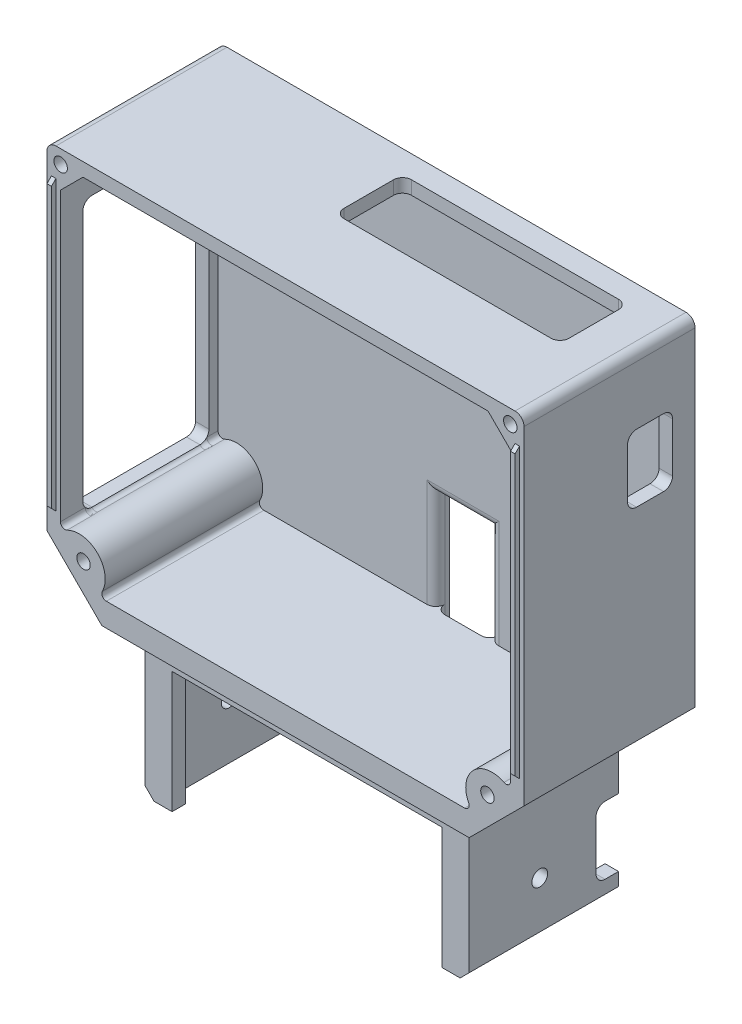
SolidWorks part; units mm, degrees
ref_plane "Front Plane" through (0, 0, 0) normal (0, 0, 1) x (1, 0, 0)
ref_plane "Top Plane" through (0, 0, 0) normal (0, 1, 0) x (1, 0, 0)
ref_plane "Right Plane" through (0, 0, 0) normal (1, 0, 0) x (0, 0, -1)
sketch "Sketch1" plane through (0, 0, 0) normal (0, 0, 1) x (1, 0, 0)
  line L1 (53, -42.5) -> (-53, -42.5)
  line L2 (53, -42.5) -> (53, 42.5)
  line L3 (53, 42.5) -> (-53, 42.5)
  line L4 (-53, -42.5) -> (-53, 42.5)
  line L5 (53, -42.5) -> (-53, 42.5) construction
  line L6 (53, 42.5) -> (-53, -42.5) construction
  point P0 (0, 0)
  dimension "D1" = 85
  dimension "D2" = 106
extrude "Boss-Extrude1" add sketch "Sketch1" along normal blind 38
chamfer "Chamfer1" distance 10 angle 45 2 edges at (-53, -42.5, 19) (53, -42.5, 19)
shell "Shell1" thickness 3 removed face at (0, -10.8333, 38)
sketch "Sketch2" plane through (0, -42.5, 0) normal (0, -1, 0) x (1, 0, 0)
  line L0 (-43, 0) -> (43, 0) construction
  line L1 (36, 0) -> (33, 0)
  line L2 (36, 0) -> (36, 33.2)
  line L7 (0, 0) -> (0, 38) construction
  line L8 (-43, 38) -> (43, 38) construction
  line L11 (-36, 0) -> (-36, 33.2)
  line L12 (-36, 0) -> (-33, 0)
  line L13 (-36, 33.2) -> (36, 33.2)
  line L14 (33, 0) -> (33, 30.2)
  line L15 (33, 30.2) -> (-33, 30.2)
  line L16 (-33, 30.2) -> (-33, 0)
  dimension "D1" = 33
  dimension "D2" = 3
  dimension "D3" = 3
  dimension "D4" = 33.2
extrude "Boss-Extrude2" add sketch "Sketch2" along normal blind 35
sketch "Sketch3" plane through (0, 0, 33.2) normal (0, 0, 1) x (1, 0, 0)
  line L0 (36, -77.5) -> (-36, -77.5) construction
  line L1 (-30, -77.5) -> (30, -77.5)
  line L2 (-30, -77.5) -> (-30, -50.5)
  line L3 (-30, -50.5) -> (30, -50.5)
  line L4 (30, -77.5) -> (30, -50.5)
  line L5 (0, -77.5) -> (0, -50.5) construction
  line L6 (-36, -77.5) -> (-36, -42.5) construction
  line L7 (36, -77.5) -> (36, -42.5) construction
  line L8 (36, -42.5) -> (-36, -42.5) construction
  dimension "D1" = 60
  dimension "D2" = 8
extrude "Cut-Extrude1" cut sketch "Sketch3" against normal through all
chamfer "Chamfer3" distance 2 angle 45 2 edges at (-36, -77.5, 16.6) (36, -77.5, 16.6)
sketch "Sketch5" plane through (-36, 0, 0) normal (-1, 0, 0) x (0, 0, 1)
  line L27 (0, -75.5) -> (0, -42.5) construction
  line L28 (0, -75.5) -> (33.2, -75.5) construction
  line L29 (0, -57.6) -> (0, -72.6)
  line L30 (0, 42.5) -> (0, -32.5) construction
  line L40 (0, -57.6) -> (3, -57.6)
  line L41 (5, -59.6) -> (5, -70.6)
  line L42 (3, -72.6) -> (0, -72.6)
  arc A8 (5, -59.6) -> (3, -57.6) centre (3, -59.6) ccw
  arc A9 (3, -72.6) -> (5, -70.6) centre (3, -70.6) ccw
  dimension "D1" = 2
  dimension "D2" = 5
  dimension "D3" = 2.9
  dimension "D4" = 17.9
extrude "Cut-Extrude3" cut sketch "Sketch5" against normal through all
sketch "Sketch4" plane through (-36, 0, 0) normal (-1, 0, 0) x (0, 0, 1)
  line L0 (30, -42.5) -> (30, -77.5) construction
  line L1 (38, -42.5) -> (0, -42.5) construction
  line L2 (33.2, -77.5) -> (0, -77.5) construction
  line L3 (33.2, -75.5) -> (33.2, -42.5) construction
  line L5 (30, -65.1) -> (5, -65.1) construction
  line L6 (5, -70.6) -> (5, -59.6) construction
  line L7 (0, -72.6) -> (3, -72.6) construction
  line L8 (3, -57.6) -> (0, -57.6) construction
  circle A0 centre (17.5, -65.1) radius 1.75
  dimension "D1" = 3.2
  dimension "D2" = 3.5
extrude "Cut-Extrude2" cut sketch "Sketch4" against normal through all
sketch "Sketch6" plane through (0, -42.5, 0) normal (0, -1, 0) x (1, 0, 0)
  line L8 (10.4, -2) -> (-1.6, -2)
  line L9 (43, 0) -> (43, 38) construction
  line L10 (-43, 38) -> (43, 38) construction
  line L19 (10.4, 1) -> (10.4, -2)
  line L20 (0.4, 3) -> (8.4, 3)
  line L21 (-1.6, -2) -> (-1.6, 1)
  arc A4 (10.4, 1) -> (8.4, 3) centre (8.4, 1) ccw
  arc A5 (0.4, 3) -> (-1.6, 1) centre (0.4, 1) ccw
  dimension "D1" = 2
  dimension "D2" = 32.6
  dimension "D3" = 44.6
  dimension "D4" = 35
  dimension "D5" = 40
extrude "Cut-Extrude4" cut sketch "Sketch6" against normal blind 25
chamfer "Chamfer4" distance 7 angle 45 3 edges at (36, -42.5, 16.6) (0, -42.5, 33.2) (-36, -42.5, 16.6)
sketch "Sketch7" plane through (-53, 0, 0) normal (-1, 0, 0) x (0, 0, 1)
  line L0 (0, 0) -> (38, 0) construction
  line L1 (38, 42.5) -> (38, -32.5) construction
  line L2 (0, 42.5) -> (0, -32.5) construction
  line L3 (5, -30) -> (33, -30)
  line L4 (5, -30) -> (5, 30)
  line L5 (5, 30) -> (33, 30)
  line L6 (33, -30) -> (33, 30)
  line L7 (5, -30) -> (33, 30) construction
  line L8 (5, 30) -> (33, -30) construction
  point P5 (19, 0)
  dimension "D1" = 5
  dimension "D2" = 28
  dimension "D3" = 60
extrude "Cut-Extrude5" cut sketch "Sketch7" against normal blind 15
sketch "Sketch8" plane through (0, 42.5, 0) normal (0, 1, 0) x (1, 0, 0)
  line L0 (53, 0) -> (-53, 0) construction
  line L5 (43, -20) -> (-7, -20)
  line L6 (43, -20) -> (43, -5)
  line L7 (43, -5) -> (-7, -5)
  line L8 (-7, -20) -> (-7, -5)
  line L9 (53, -38) -> (53, 0) construction
  dimension "D1" = 5
  dimension "D2" = 10
  dimension "D3" = 50
  dimension "D4" = 15
extrude "Cut-Extrude6" cut sketch "Sketch8" against normal blind 15
sketch "Sketch9" plane through (53, 0, 0) normal (1, 0, 0) x (0, 0, -1)
  line L0 (0, -32.5) -> (0, 42.5) construction
  line L1 (-5, 27.5) -> (-15, 27.5)
  line L2 (-5, 27.5) -> (-5, 12.5)
  line L3 (-5, 12.5) -> (-15, 12.5)
  line L4 (-15, 27.5) -> (-15, 12.5)
  line L5 (-38, 42.5) -> (0, 42.5) construction
  dimension "D1" = 5
  dimension "D2" = 15
  dimension "D3" = 10
  dimension "D4" = 15
extrude "Cut-Extrude7" cut sketch "Sketch9" against normal blind 15
fillet "Fillet3" radius 2 15 edges at (51.5, 12.5, 15) (51.5, 27.5, 15) (51.5, 27.5, 5) (51.5, 12.5, 5) (43, 41, 20) (-7, 41, 20) (43, 41, 5) (-7, 41, 5) (-51.5, 30, 33) (-51.5, -30, 33) (-51.5, -30, 5) (-51.5, 30, 5) (4.4, -17.5, 3) (0.4, -28.5, 3) (8.4, -28.5, 3)
sketch "Sketch10" plane through (0, 0, 38) normal (0, 0, 1) x (1, 0, 0)
  line L0 (-51.5, -34) -> (-51.5, 42.5) construction
  line L1 (-53, -32.5) -> (-43, -42.5) construction
  line L2 (53, 42.5) -> (-53, 42.5) construction
  line L3 (-53, 42.5) -> (-53, -32.5) construction
  line L4 (-50, 39.5) -> (-50, -31.2574) construction
  line L6 (-51, -25.75) -> (-52, -25.75)
  line L7 (-51, -25.75) -> (-51, 34.25)
  line L8 (-51, 34.25) -> (-52, 34.25)
  line L9 (-52, -25.75) -> (-52, 34.25)
  line L10 (-51, -25.75) -> (-52, 34.25) construction
  line L11 (-51, 34.25) -> (-52, -25.75) construction
  point P10 (-51.5, 4.25)
  dimension "D1" = 1
  dimension "D2" = 60
extrude "Boss-Extrude3" add sketch "Sketch10" along normal blind 1
chamfer "Chamfer5" distance 2 angle 45 2 edges at (-51.5, 34.25, 38) (-51.5, -25.75, 38)
ref_plane "Plane1" through (0, 0, 0) normal (-1, 0, 0) x (0, 0, 1)
mirror "Mirror1" about plane through (0, 0, 0) normal (-1, 0, 0) of "Chamfer5", "Boss-Extrude3"
fillet "Fillet5" radius 2 2 edges at (-53, 42.5, 19) (53, 42.5, 19)
chamfer "Chamfer6" distance 5 angle 45 2 edges at (-50, 39.5, 20.5) (50, 39.5, 20.5)
sketch "Sketch12" plane through (0, 0, 38) normal (0, 0, 1) x (1, 0, 0)
  line L0 (41.7574, -39.5) -> (50, -31.2574) construction
  line L1 (50, -31.2574) -> (41.7574, -39.5) construction
  line L2 (50, -31.2574) -> (50, 34.5) construction
  line L3 (50, -31.2574) -> (41.7574, -39.5)
  line L4 (0, 20.9) -> (0, -20.9) construction
  line L5 (-50, -31.2574) -> (-41.7574, -39.5)
  arc A0 (41.7574, -39.5) -> (50, -31.2574) centre (45.8787, -35.3787) cw
  arc A1 (-41.7574, -39.5) -> (-50, -31.2574) centre (-45.8787, -35.3787) ccw
extrude "Boss-Extrude4" add sketch "Sketch12" against normal up to surface (35 mm away) up to face at (1.4667, -8.6262, 3)
sketch "Sketch13" plane through (0, 0, 38) normal (0, 0, 1) x (1, 0, 0)
  line L0 (-41.7574, -31.2574) -> (-48, -37.5) construction
  line L2 (0, 20.9) -> (0, -20.9) construction
  line L3 (-53, -32.5) -> (-43, -42.5) construction
  line L4 (41.7574, -31.2574) -> (48, -37.5) construction
  arc A2 (-41.7574, -39.5) -> (-50, -31.2574) centre (-45.8787, -35.3787) ccw construction
  circle A3 centre (-44.8787, -34.3787) radius 1.5
  circle A4 centre (44.8787, -34.3787) radius 1.5
  dimension "D1" = 3
extrude "Cut-Extrude9" cut sketch "Sketch13" against normal up to surface (35 mm away) up to face at (1.4667, -7.9393, 3)
fillet "Fillet6" radius 1 4 edges at (50, -31.2574, 20.5) (41.7574, -39.5, 20.5) (-41.7574, -39.5, 20.5) (-50, -31.2574, 20.5)
sketch "Sketch11" plane through (0, 0, 38) normal (0, 0, 1) x (1, 0, 0)
  line L0 (-47.5, 37) -> (-52.4142, 41.9142) construction
  line L1 (-50, 34.5) -> (-45, 39.5) construction
  line L2 (0, 20.9) -> (0, -20.9) construction
  line L3 (47.5, 37) -> (52.4142, 41.9142) construction
  circle A0 centre (-49.9571, 39.4571) radius 1.5
  arc A2 (-51, 42.5) -> (-53, 40.5) centre (-51, 40.5) ccw construction
  circle A3 centre (49.9571, 39.4571) radius 1.5
  point P13 (0, 0)
  point P14 (-49.9571, 39.4571)
  dimension "D1" = 3
extrude "Cut-Extrude8" cut sketch "Sketch11" against normal blind 5
